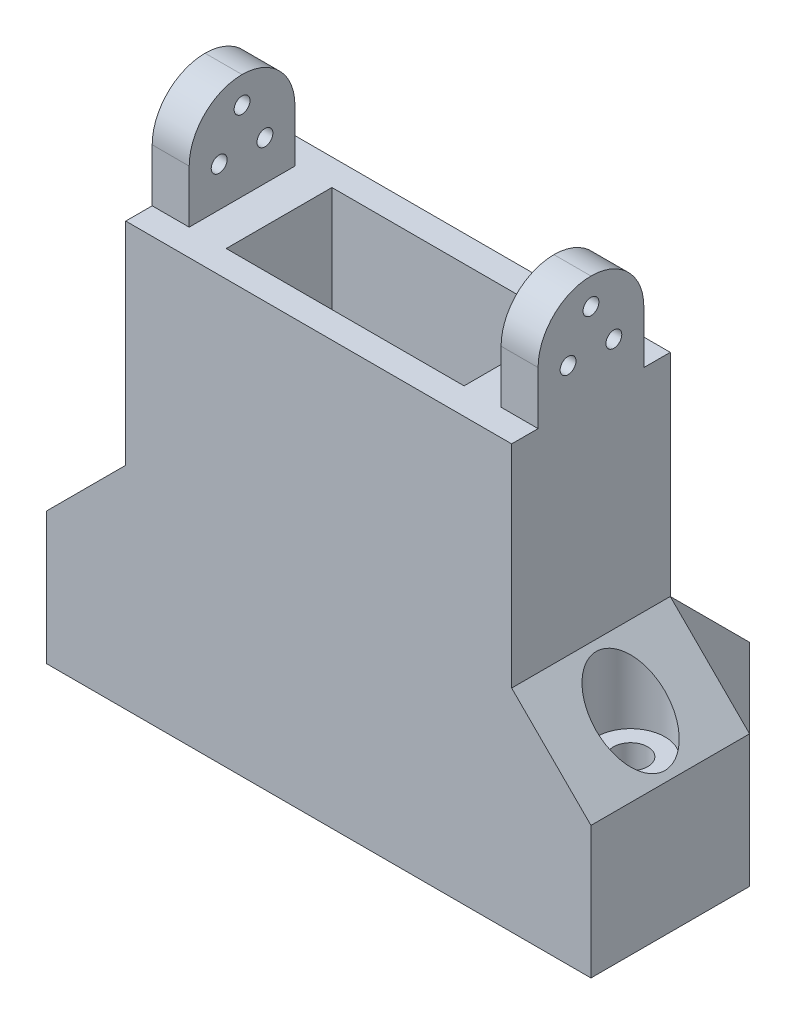
SolidWorks part; units mm, degrees
ref_plane "Alzado" through (0, 0, 0) normal (0, 0, 1) x (1, 0, 0)
ref_plane "Planta" through (0, 0, 0) normal (0, 1, 0) x (1, 0, 0)
ref_plane "Vista lateral" through (0, 0, 0) normal (1, 0, 0) x (0, 0, -1)
sketch "Sketch1" plane through (0, 0, 0) normal (0, 0, 1) x (1, 0, 0)
  line L0 (0, 40) -> (-15, 25)
  line L1 (0, 0) -> (73, 0)
  line L2 (0, 40) -> (0, 80)
  line L3 (0, 80) -> (73, 80)
  line L4 (73, 40) -> (73, 80)
  line L5 (-15, 0) -> (0, 0)
  line L6 (73, 0) -> (88, 0)
  line L7 (88, 25) -> (73, 40)
  line L8 (-15, 0) -> (-15, 25)
  line L9 (88, 0) -> (88, 25)
  dimension "D1" = 73
  dimension "D2" = 80
  dimension "D3" = 45
  dimension "D4" = 25
  dimension "D5" = 45
  dimension "D6" = 25
  dimension "D7" = 15
  dimension "D8" = 15
extrude "Boss-Extrude1" add sketch "Sketch1" along normal blind 30
sketch "Sketch2" plane through (0, 0, 0) normal (0, -1, 0) x (1, 0, 0)
  line L0 (-15, 30) -> (-15, 0) construction
  line L1 (14, 25) -> (59, 25)
  line L2 (14, 25) -> (14, 5)
  line L3 (14, 5) -> (59, 5)
  line L4 (59, 25) -> (59, 5)
  line L5 (-15, 0) -> (88, 0) construction
  line L6 (-15, 30) -> (88, 30) construction
  line L7 (88, 30) -> (88, 0) construction
  circle A0 centre (-7.5, 15) radius 3.25
  circle A1 centre (80.5, 15) radius 3.25
  dimension "D3" = 6.5
  dimension "D6" = 6.5
  dimension "D1" = 7.5
  dimension "D2" = 15
  dimension "D4" = 15
  dimension "D5" = 7.5
  dimension "D7" = 20
  dimension "D8" = 5
  dimension "D9" = 45
  dimension "D10" = 29
extrude "Cut-Extrude1" cut sketch "Sketch2" against normal blind 90
sketch "Sketch3" plane through (0, 80, 0) normal (0, 1, 0) x (1, 0, 0)
  line L1 (0, -5) -> (7, -5)
  line L2 (0, -5) -> (0, -25)
  line L3 (0, -25) -> (7, -25)
  line L4 (7, -5) -> (7, -25)
  line L5 (73, -30) -> (0, -30) construction
  line L6 (73, -5) -> (66, -5)
  line L7 (73, -5) -> (73, -25)
  line L8 (73, -25) -> (66, -25)
  line L9 (66, -5) -> (66, -25)
  dimension "D1" = 7
  dimension "D2" = 7
  dimension "D3" = 20
  dimension "D4" = 20
  dimension "D5" = 5
  dimension "D6" = 5
  dimension "D7" = 59
extrude "Boss-Extrude2" add sketch "Sketch3" along normal blind 20
sketch "Sketch4" plane through (73, 0, 0) normal (1, 0, 0) x (0, 0, -1)
  line L0 (-5, 100) -> (-5, 80) construction
  line L1 (-25, 100) -> (-5, 100) construction
  line L2 (-15, 90) -> (-15, 95) construction
  line L3 (-15, 90) -> (-10.6699, 87.5) construction
  line L4 (-15, 90) -> (-19.3301, 87.5) construction
  circle A0 centre (-15, 90) radius 5 construction
  circle A1 centre (-15, 95) radius 1.5
  circle A2 centre (-10.6699, 87.5) radius 1.5
  circle A3 centre (-19.3301, 87.5) radius 1.5
  dimension "D1" = 10
  dimension "D6" = 3
  dimension "D7" = 3
  dimension "D8" = 3
  dimension "D2" = 10
  dimension "D3" = 10
  dimension "D4" = 120
  dimension "D5" = 120
extrude "Cut-Extrude2" cut sketch "Sketch4" against normal blind 80
fillet "Fillet1" radius 10 4 edges at (3.5, 100, 25) (69.5, 100, 25) (3.5, 100, 5) (69.5, 100, 5)
sketch "Sketch5" plane through (0, 0, 0) normal (0, -1, 0) x (1, 0, 0)
  circle A0 centre (-7.5, 15) radius 6.5
  circle A1 centre (80.5, 15) radius 6.5
  dimension "D1" = 13
  dimension "D2" = 13
extrude "Cut-Extrude3" cut sketch "Sketch5" against normal blind 17 from offset 25 offset against normal yes
sketch "Sketch6" plane through (0, 0, 0) normal (1, 0, 0) x (0, 0, -1)
  line L0 (0, 40) -> (0, 0)
  line L1 (0, 0) -> (15, 0)
  line L2 (15, 0) -> (15, 25)
  line L3 (15, 25) -> (0, 40)
  dimension "D1" = 15
  dimension "D2" = 25
  dimension "D3" = 45
extrude "Boss-Extrude3" add sketch "Sketch6" along normal blind 73
sketch "Sketch7" plane through (0, 0, 0) normal (0, -1, 0) x (1, 0, 0)
  line L0 (73, -15) -> (0, -15) construction
  line L1 (73, 0) -> (73, -15) construction
  circle A0 centre (36.5, -7.5) radius 3.25
  dimension "D1" = 6.5
  dimension "D2" = 7.5
  dimension "D3" = 36.5
extrude "Cut-Extrude4" cut sketch "Sketch7" against normal blind 40
sketch "Sketch8" plane through (0, 0, 0) normal (0, -1, 0) x (1, 0, 0)
  circle A0 centre (36.5, -7.5) radius 6.5
  dimension "D1" = 13
extrude "Cut-Extrude5" cut sketch "Sketch8" against normal blind 17 from offset 25 offset against normal yes
